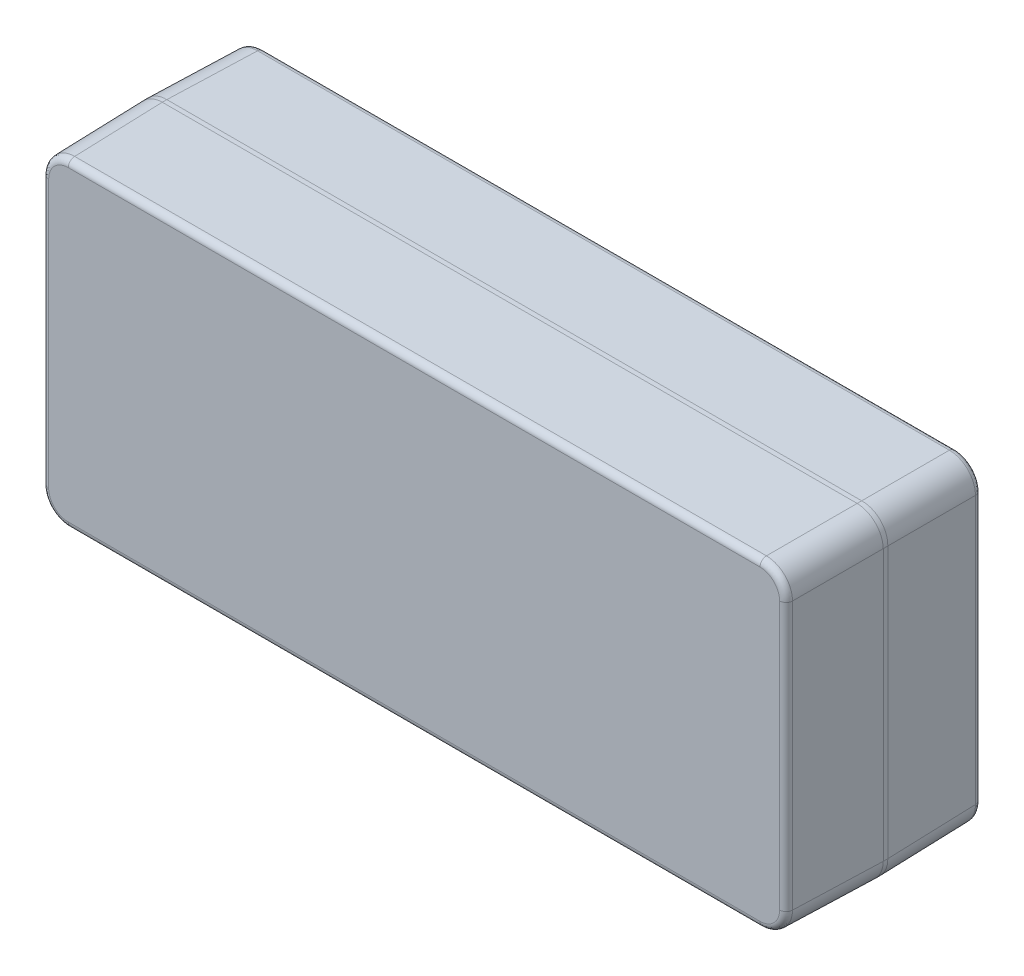
SolidWorks part; units mm, degrees
material "ABS"
ref_plane "Front Plane" through (0, 0, 0) normal (0, 0, 1) x (1, 0, 0)
ref_plane "Top Plane" through (0, 0, 0) normal (0, 1, 0) x (1, 0, 0)
ref_plane "Right Plane" through (0, 0, 0) normal (1, 0, 0) x (0, 0, -1)
sketch "Sketch1" plane through (0, 0, 0) normal (0, 0, 1) x (1, 0, 0)
  line L1 (-57, -24.5) -> (57, -24.5)
  line L2 (-57, -24.5) -> (-57, 24.5)
  line L3 (-57, 24.5) -> (57, 24.5)
  line L4 (57, -24.5) -> (57, 24.5)
  line L5 (0, 24.5) -> (0, -24.5) construction
  line L6 (-57, 0) -> (57, 0) construction
  point P0 (0, 0)
  dimension "D1" = 114
  dimension "D2" = 49
extrude "Boss-Extrude1" add sketch "Sketch1" against normal blind 15 draft 1 draft outward yes
mirror "Mirror1" about plane through (0, 0, -15) normal (0, 0, -1) of "Boss-Extrude1"
fillet "Fillet1" radius 20 4 edges at (0, 24.7618, -15) (-57.2618, 0, -15) (0, -24.7618, -15) (57.2618, 0, -15)
fillet "Fillet2" radius 4 12 edges at (57.1279, 24.6279, -7.3255) (57.2588, 24.7588, -15) (-57.1279, 24.6279, -7.3255) (-57.2588, 24.7588, -15) (-57.1279, -24.6279, -7.3255) (-57.2588, -24.7588, -15) (57.1279, -24.6279, -7.3255) (57.2588, -24.7588, -15) (57.1279, 24.6279, -22.6745) (-57.1279, 24.6279, -22.6745) (-57.1279, -24.6279, -22.6745) (57.1279, -24.6279, -22.6745)
fillet "Fillet3" radius 1 16 edges at (55.8287, -23.3287, 0) (0, -24.5, 0) (-55.8287, -23.3287, 0) (-57, 0, 0) (-55.8287, 23.3287, 0) (0, 24.5, 0) (55.8287, 23.3287, 0) (57, 0, 0) (-55.8287, 23.3287, -30) (-57, 0, -30) (-55.8287, -23.3287, -30) (0, -24.5, -30) (55.8287, -23.3287, -30) (57, 0, -30) (55.8287, 23.3287, -30) (0, 24.5, -30)
